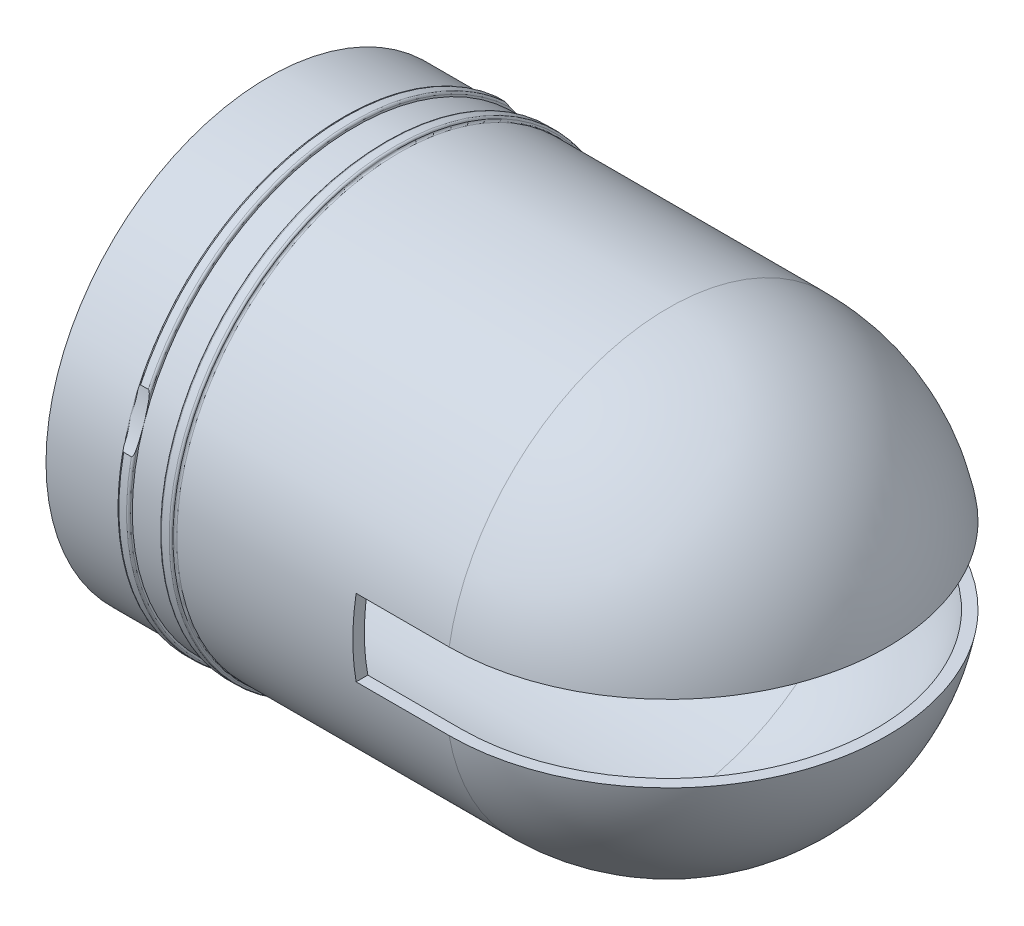
SolidWorks part; units mm, degrees
ref_plane "Front Plane" through (0, 0, 0) normal (0, 0, 1) x (1, 0, 0)
ref_plane "Top Plane" through (0, 0, 0) normal (0, 1, 0) x (1, 0, 0)
ref_plane "Right Plane" through (0, 0, 0) normal (1, 0, 0) x (0, 0, -1)
sketch "Sketch1" plane through (0, 0, 0) normal (0, 1, 0) x (1, 0, 0)
  line L0 (0, 58) -> (-55, 58) construction
  line L1 (-55, 58) -> (-55, -58) construction
  line L2 (-55, -58) -> (0, -58) construction
  line L3 (0, 55) -> (-55, 55) construction
  line L4 (-52, 55) -> (-52, -55) construction
  line L5 (-55, -55) -> (0, -55) construction
  line L6 (-52, -55) -> (0, -55) construction
  line L7 (0, 55) -> (-52, 55) construction
  line L8 (0, 0) -> (58, 0)
  line L9 (58, 0) -> (0, 0) construction
  line L10 (0, 0) -> (0, -58)
  circle A0 centre (0, 0) radius 55
  circle A1 centre (0, 0) radius 58
  dimension "D1" = 110
  dimension "D3" = 55
  dimension "D2" = 3
  dimension "D4" = 3
revolve "Revolve2" add sketch "Sketch1" angle 360 about L8 region at (56.5, 0, 0.8202)
sketch "Sketch5" plane through (0, 0, 0) normal (-1, 0, 0) x (0, 0, 1)
  circle A0 centre (0, 0) radius 55 construction
  circle A1 centre (0, 0) radius 58
  circle A2 centre (0, 0) radius 58
  circle A3 centre (0, 0) radius 55
  dimension "D1" = 0
extrude "Boss-Extrude3" add sketch "Sketch5" along normal blind 104.25
sketch "Sketch6" plane through (0, 0, 0) normal (0, 0, 1) x (1, 0, 0)
  line L0 (-104.25, 58) -> (-104.25, -58) construction
  line L1 (-104.25, 58) -> (-104.25, -58)
  line L2 (-104.25, 0) -> (46.43, 0) construction
  line L4 (-100, 10) -> (100, 10)
  line L5 (-100, 10) -> (-100, -10)
  line L6 (-100, -10) -> (100, -10)
  line L7 (100, 10) -> (100, -10)
  line L8 (-100, 10) -> (100, -10) construction
  line L9 (-100, -10) -> (100, 10) construction
  point P5 (0, 0)
  dimension "D1" = 20
  dimension "D2" = 200
extrude "Cut-Extrude1" cut sketch "Sketch6" against normal through all both and the other way through all contours L7 L4 L1 L6 | L5 L6 L1 L4 region at (0, 0, 0)
sketch "Sketch7" plane through (-104.25, 0, 0) normal (-1, 0, 0) x (0, 0, 1)
  line L8 (-57.1314, 10) -> (-54.0833, 10)
  line L9 (54.0833, 10) -> (57.1314, 10)
  circle A0 centre (0, 0) radius 55
  circle A1 centre (0, 0) radius 58
  circle A2 centre (0, 0) radius 58
  circle A4 centre (0, 0) radius 58
  arc A8 (57.1314, 10) -> (-57.1314, 10) centre (0, 0) ccw
  arc A9 (54.0833, 10) -> (-54.0833, 10) centre (0, 0) ccw
  circle M10 centre (0, 0) radius 58
  circle M12 centre (0, 0) radius 55
  dimension "D1" = 0
extrude "Boss-Extrude4" add sketch "Sketch7" against normal blind 80 contours L9 L8 M12 M10 | L9 L8 M12 M10 region at (-104.25, 56.7606, 0) region at (-104.25, 8.6554, -55.6073)
thread "MinColWidth_OnTracking1" pitch 2 method extrude profile "HeaderRowsCount1" start angle 291, offset 0, length 4, pitch 2.5, diameter 110
ref_plane "Plane1" through (-104.25, -51.3469, -19.7102) normal (0, -0.3584, 0.9336) x (0, -0.9336, -0.3584)
sketch "HeaderRowsCount1" plane through (-104.25, -51.3469, -19.7102) normal (0, -0.3584, 0.9336) x (0, -0.9336, -0.3584)
  line L0 (0, 0) -> (0, 2) construction
  line L11 (0, 0) -> (0, 1.75)
  line L12 (0, 1.75) -> (-1.0825, 1.125)
  line L13 (-1.0825, 1.125) -> (-1.0825, 0.625)
  line L15 (-1.0825, 0.625) -> (0, 0)
  line L17 (-1.0825, 0.875) -> (0, 0.875) construction
  point P2 (0, 0)
  dimension "Pitch" = 2
  dimension "Profile_Angle" = 60
  dimension "Profile_Land" = 0.5
  dimension "Profile_Height" = 1.0825
ref_plane "Plane2" through (-73.65, 0, 0) normal (1, 0, 0) x (0, 0, -1)
sketch "Sketch10" plane through (-73.65, 0, 0) normal (1, 0, 0) x (0, 0, -1)
  circle A1 centre (0, 0) radius 58 construction
  circle A2 centre (0, 0) radius 59
  circle A3 centre (0, 0) radius 59
  circle A4 centre (0, 0) radius 58
  dimension "D1" = 1
extrude "Boss-Extrude5" add sketch "Sketch10" along normal blind 3
fillet "Fillet1" radius 0.5 2 edges at (-70.65, 58, 0) (-70.65, 59, 0)
ref_plane "Plane3" through (-81.55, 0, 0) normal (-1, 0, 0) x (0, 0, 1)
ref_plane "Plane4" through (-81.75, 0, 0) normal (-1, 0, 0) x (0, 0, 1)
sketch "Sketch11" plane through (-81.75, 0, 0) normal (-1, 0, 0) x (0, 0, 1)
  circle A0 centre (0, 0) radius 58 construction
  circle A1 centre (0, 0) radius 59
  circle A2 centre (0, 0) radius 59
  circle A3 centre (0, 0) radius 58
  dimension "D1" = 0
extrude "Boss-Extrude6" add sketch "Sketch11" along normal blind 3
fillet "Fillet2" radius 0.5 5 edges at (-81.75, 0, 59) (-84.75, 0, 59) (-73.65, 58, 0) (-73.65, 59, 0) (-84.75, 0, 58)
sketch "Sketch12" plane through (-81.55, 0, 0) normal (1, 0, 0) x (0, 0, -1)
  circle A0 centre (19.4173, -96.0571) radius 40
  circle A1 centre (0, 0) radius 58 construction
  circle A2 centre (0, 0) radius 58
  dimension "D1" = 80
extrude "Cut-Extrude2" cut sketch "Sketch12" against normal through all and the other way blind 5 contours A0 | A0 region at (-81.55, -96.0571, -19.4173)
pattern_circular "CirPattern1" count 3 over 240 about axis through (-104.25, 0, 0) along (1, 0, 0) of "Cut-Extrude2" reverse direction yes
